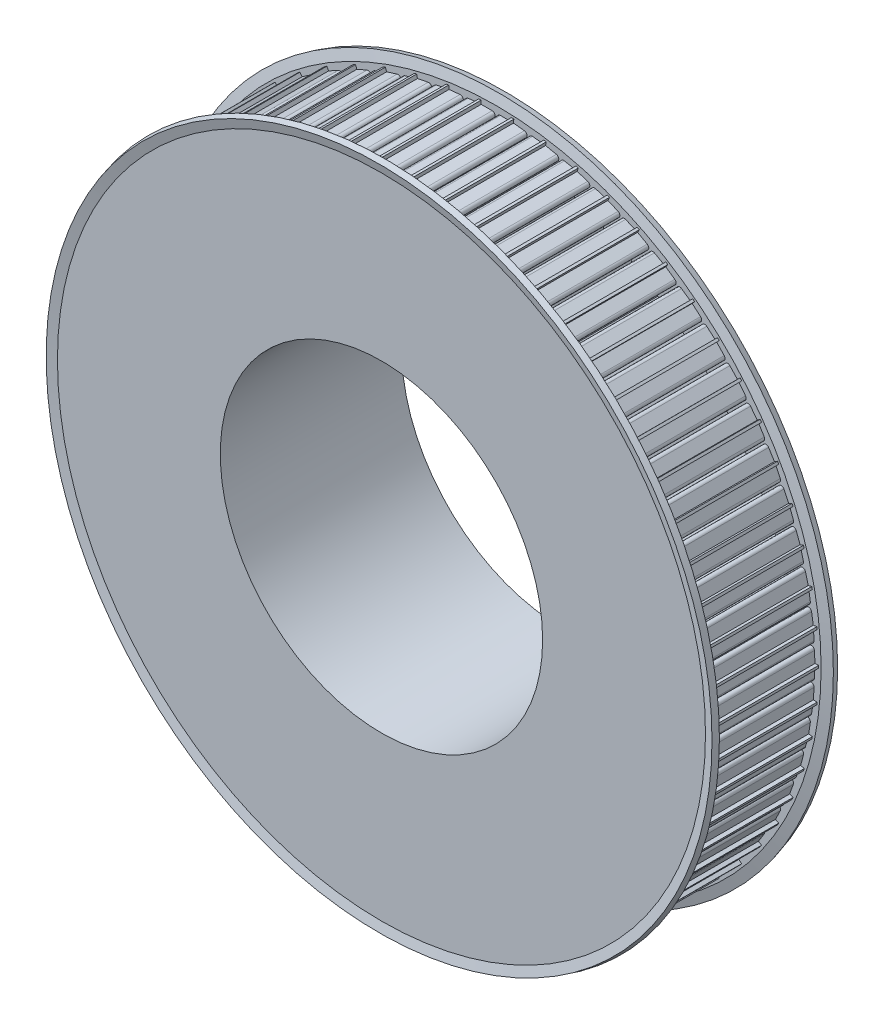
SolidWorks part; units mm, degrees
ref_plane "Front Plane" through (0, 0, 0) normal (0, 0, 1) x (1, 0, 0)
ref_plane "Top Plane" through (0, 0, 0) normal (0, 1, 0) x (1, 0, 0)
ref_plane "Right Plane" through (0, 0, 0) normal (1, 0, 0) x (0, 0, -1)
ref_axis "Axis1" through (0, 0, 55) along (0, 0, -1)
sketch "Sketch1" plane through (0, 0, 0) normal (1, 0, 0) x (0, 0, -1)
  line L0 (0, 40) -> (0, 80)
  line L1 (0, 80) -> (30, 80)
  line L2 (30, 80) -> (30, 55.5)
  line L3 (30, 55.5) -> (45, 55.5)
  line L4 (45, 55.5) -> (45, 40)
  line L5 (45, 40) -> (0, 40)
  dimension "D1" = 40
  dimension "D2" = 30
  dimension "D3" = 15
  dimension "D4" = 15.5
  dimension "D5" = 40
revolve "Revolve1" add sketch "Sketch1" angle 360 about axis through (0, 0, 55) along (0, 0, -1)
sketch "Sketch2" plane through (0, 0, 0) normal (0, 0, 1) x (1, 0, 0)
  line L0 (1.0152, 79) -> (3.75, 79)
  line L1 (-3.75, 81) -> (3.75, 81)
  line L2 (-3.75, 81) -> (-3.75, 79)
  line L3 (-3.75, 79) -> (-1.0152, 79)
  line L4 (3.75, 81) -> (3.75, 79)
  line L5 (1.199, 71.89) -> (-1.199, 71.89)
  arc A0 (-0.8121, 77.528) -> (-1.199, 71.89) centre (0, 74.64) ccw
  arc A1 (-0.8121, 77.528) -> (-1.0152, 79) centre (-1.0152, 78.25) ccw
  arc A2 (0.8121, 77.528) -> (1.0152, 79) centre (1.0152, 78.25) cw
  arc A3 (1.199, 71.89) -> (0.8121, 77.528) centre (0, 74.64) ccw
  point P10 (0, 0)
  dimension "D3" = 3
  dimension "D6" = 0.75
  dimension "D1" = 2
  dimension "D2" = 7.5
  dimension "D4" = 79
  dimension "D5" = 2.75
extrude "Cut-Extrude1" cut sketch "Sketch2" against normal through all
pattern_circular "CirPattern1" count 62 over 360 about axis through (0, 0, 55) along (0, 0, -1) of "Cut-Extrude1"
sketch "Sketch3" plane through (0, 0, 0) normal (1, 0, 0) x (0, 0, -1)
  line L0 (0, 77.2124) -> (0, 71.6425) construction
  line L1 (0, 71.8373) -> (1.5, 71.8373)
  line L2 (0, 71.8373) -> (0, 80.6121)
  line L3 (0, 80.6121) -> (1.5, 80.6121) construction
  line L4 (1.5, 71.8373) -> (1.5, 80.6121)
  line L5 (1.5, 80.6121) -> (0.0511, 80.2238) construction
  line L6 (1.5, 80.6121) -> (0.8569, 83.0121)
  line L7 (0.0511, 80.2238) -> (-0.592, 82.6238)
  line L8 (0.8569, 83.0121) -> (-0.592, 82.6238)
  line L9 (30, 79.9121) -> (0, 79.9121) construction
  line L10 (15, 79.8814) -> (15, 17.499) construction
  line L11 (0, 79.8814) -> (30, 79.8814) construction
  line L12 (28.5, 80.6121) -> (29.9489, 80.2238) construction
  line L13 (30, 80.6121) -> (28.5, 80.6121) construction
  line L14 (29.1431, 83.0121) -> (30.592, 82.6238)
  line L15 (29.9489, 80.2238) -> (30.592, 82.6238)
  line L16 (28.5, 80.6121) -> (29.1431, 83.0121)
  line L17 (28.5, 71.8373) -> (28.5, 80.6121)
  line L18 (30, 71.8373) -> (30, 80.6121)
  line L19 (30, 71.8373) -> (28.5, 71.8373)
  dimension "D1" = 1.5
  dimension "D3" = 1.5
  dimension "D4" = 2.4
  dimension "D5" = 165
  dimension "D6" = 0.7
revolve "Revolve3" add sketch "Sketch3" angle 360 about axis through (0, 0, 55) along (0, 0, -1) region at (0, 77.3601, -0.6878) region at (0, 77.3601, -29.3122)
